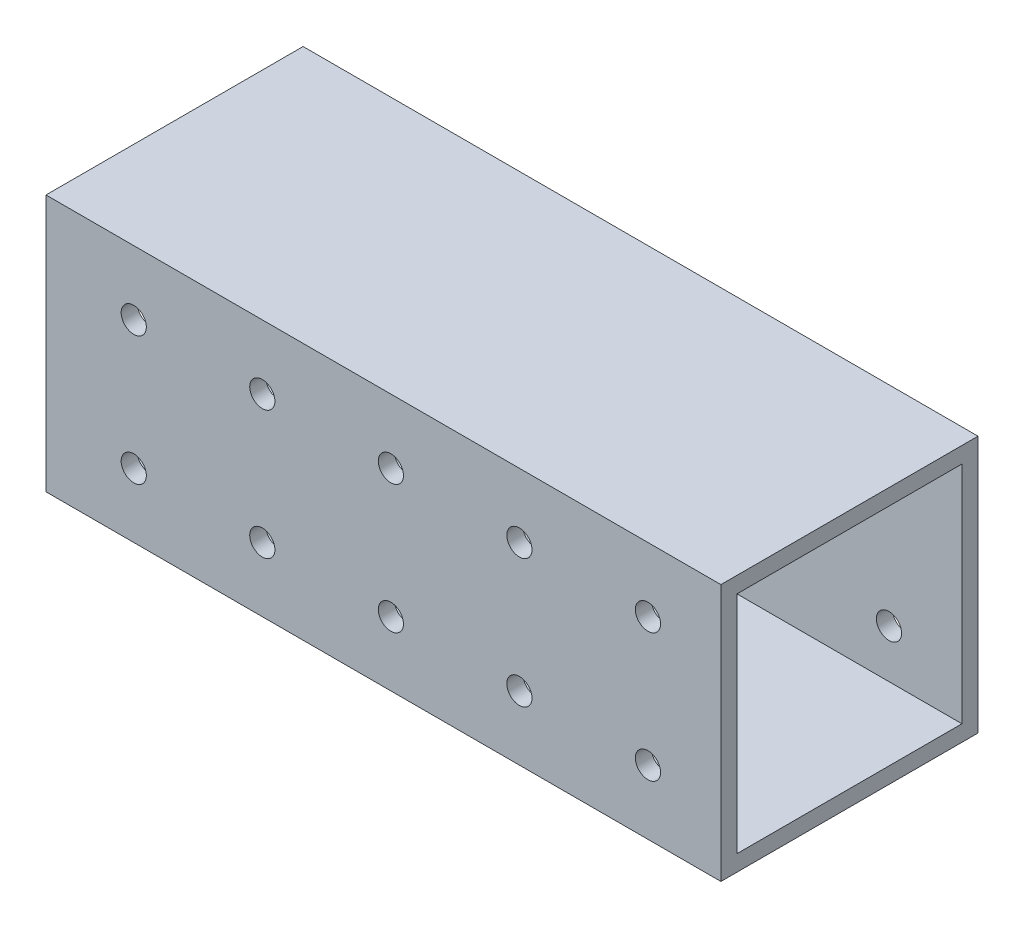
SolidWorks part; units mm, degrees
material "6061-T6 (SS)"
ref_plane "Front Plane" through (0, 0, 0) normal (0, 0, 1) x (1, 0, 0)
ref_plane "Top Plane" through (0, 0, 0) normal (0, 1, 0) x (1, 0, 0)
ref_plane "Right Plane" through (0, 0, 0) normal (1, 0, 0) x (0, 0, -1)
sketch "Sketch1" plane through (0, 0, 0) normal (1, 0, 0) x (0, 0, -1)
  line L1 (0, 0) -> (50.8, 0)
  line L2 (0, 0) -> (0, 50.8)
  line L3 (0, 50.8) -> (50.8, 50.8)
  line L4 (50.8, 0) -> (50.8, 50.8)
  dimension "D1" = 50.8
extrude "Boss-Extrude1" add sketch "Sketch1" along normal blind 133.35
shell "Shell1" thickness 3.175 removed face at (0, 25.4, -25.4) removed face at (133.35, 25.4, -25.4)
sketch "Sketch2" plane through (0, 0, -50.8) normal (0, 0, -1) x (-1, 0, 0)
  circle A0 centre (-118.9383, 38.1) radius 2.4892 construction
  circle A1 centre (-93.5383, 38.1) radius 2.4892 construction
  circle A2 centre (-68.1383, 38.1) radius 2.4892 construction
  circle A3 centre (-42.7383, 38.1) radius 2.4892 construction
  circle A4 centre (-17.3383, 38.1) radius 2.4892 construction
  circle A5 centre (-17.3383, 12.7) radius 2.4892 construction
  circle A6 centre (-42.7383, 12.7) radius 2.4892 construction
  circle A7 centre (-68.1383, 12.7) radius 2.4892 construction
  circle A8 centre (-93.5383, 12.7) radius 2.4892 construction
  circle A9 centre (-118.9383, 12.7) radius 2.4892 construction
  circle A10 centre (-118.9383, 38.1) radius 2.4892
  circle A11 centre (-93.5383, 38.1) radius 2.4892
  circle A12 centre (-68.1383, 38.1) radius 2.4892
  circle A13 centre (-42.7383, 38.1) radius 2.4892
  circle A14 centre (-17.3383, 38.1) radius 2.4892
  circle A15 centre (-17.3383, 12.7) radius 2.4892
  circle A16 centre (-42.7383, 12.7) radius 2.4892
  circle A17 centre (-68.1383, 12.7) radius 2.4892
  circle A18 centre (-93.5383, 12.7) radius 2.4892
  circle A19 centre (-118.9383, 12.7) radius 2.4892
extrude "Cut-Extrude1" cut sketch "Sketch2" against normal through all
